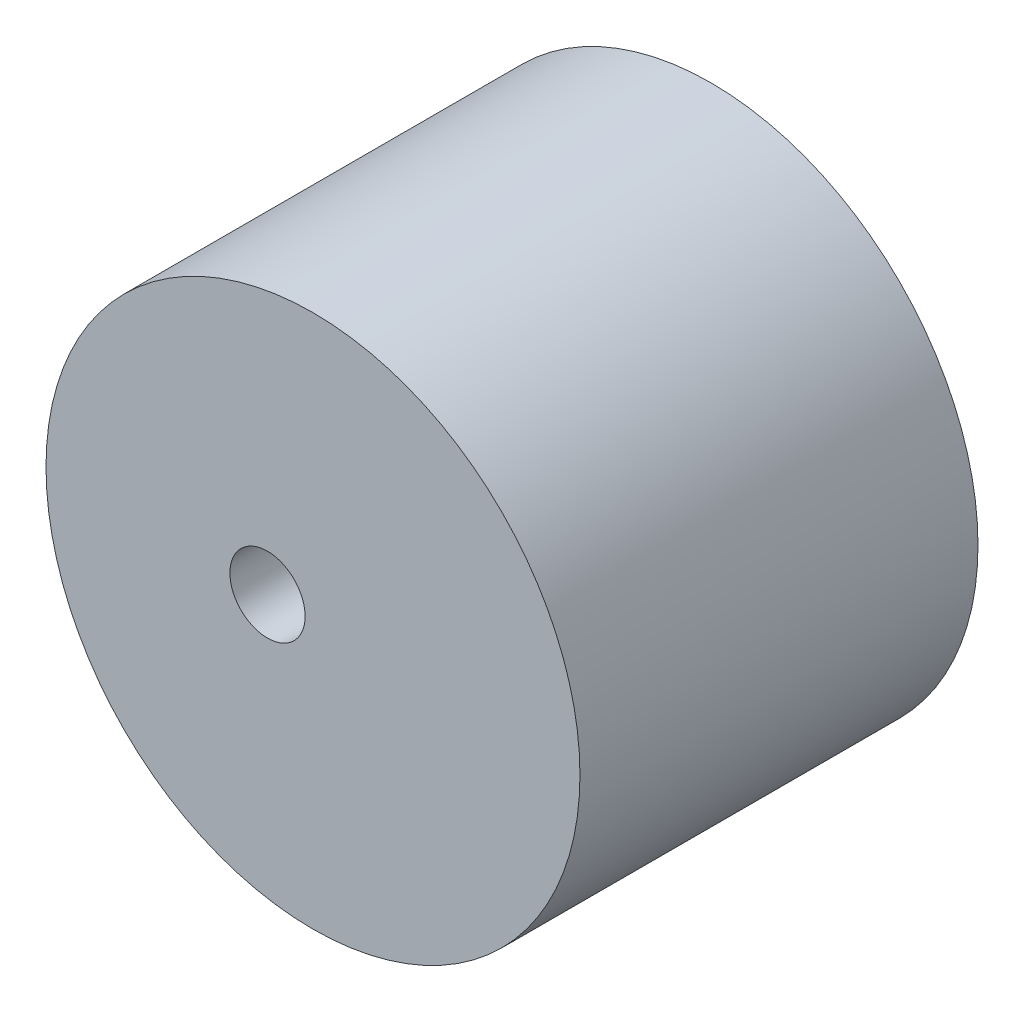
SolidWorks part; units mm, degrees
ref_plane "Front Plane" through (0, 0, 0) normal (0, 0, 1) x (1, 0, 0)
ref_plane "Top Plane" through (0, 0, 0) normal (0, 1, 0) x (1, 0, 0)
ref_plane "Right Plane" through (0, 0, 0) normal (1, 0, 0) x (0, 0, -1)
sketch "Sketch11" plane through (0, 0, 0) normal (0, 0, 1) x (1, 0, 0)
  circle A0 centre (0, 0) radius 23.4769
  circle A1 centre (-4, 0) radius 3.3085
extrude "Boss-Extrude13" add sketch "Sketch11" along normal blind 35
